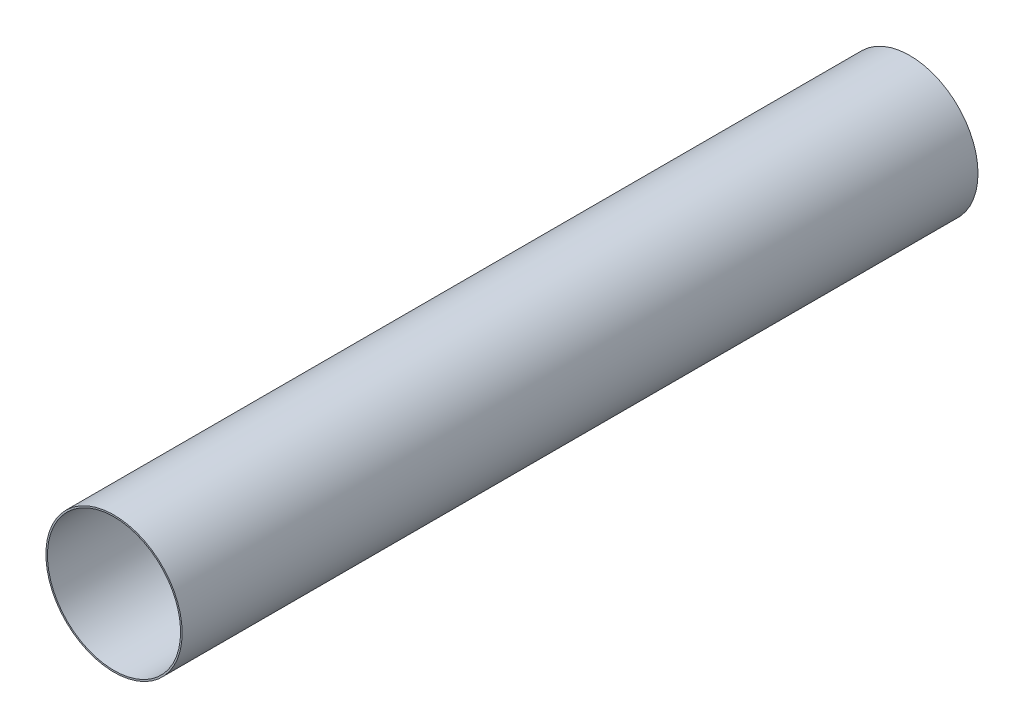
SolidWorks part; units mm, degrees
material "Thornel Mat VMA"
ref_plane "Front Plane" through (0, 0, 0) normal (0, 0, 1) x (1, 0, 0)
ref_plane "Top Plane" through (0, 0, 0) normal (0, 1, 0) x (1, 0, 0)
ref_plane "Right Plane" through (0, 0, 0) normal (1, 0, 0) x (0, 0, -1)
sketch "Sketch1" plane through (0, 0, 0) normal (0, 0, 1) x (1, 0, 0)
  circle A0 centre (0, 0) radius 86.9998
  circle A1 centre (0, 0) radius 84.9998
  dimension "D1" = 169.9997
  dimension "D2" = 173.9997
extrude "Boss-Extrude1" add sketch "Sketch1" along normal mid plane 1016
